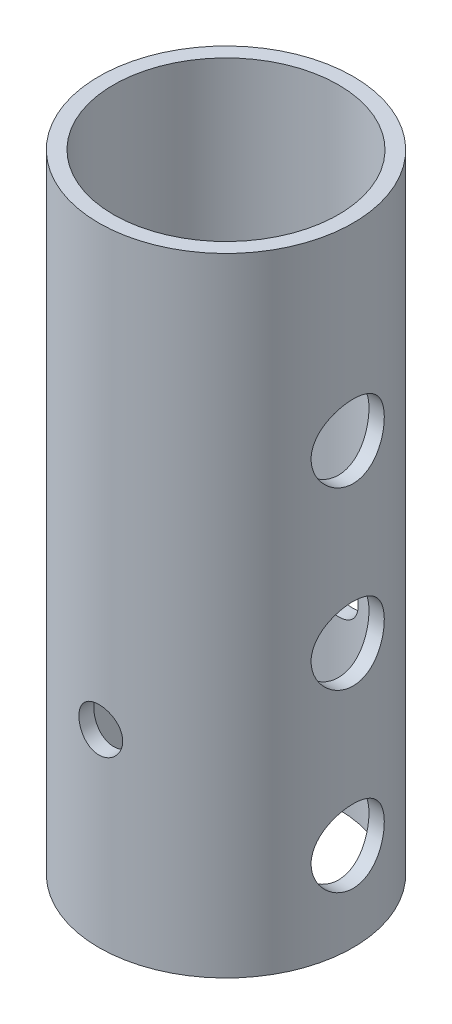
SolidWorks part; units mm, degrees
material "PTFE (general)"
ref_plane "Front Plane" through (0, 0, 0) normal (0, 0, 1) x (1, 0, 0)
ref_plane "Top Plane" through (0, 0, 0) normal (0, 1, 0) x (1, 0, 0)
ref_plane "Right Plane" through (0, 0, 0) normal (1, 0, 0) x (0, 0, -1)
sketch "Sketch1" plane through (0, 0, 0) normal (0, 1, 0) x (1, 0, 0)
  circle A0 centre (0, 0) radius 43.5
  circle A1 centre (0, 0) radius 38.5
  dimension "D1" = 87
  dimension "D2" = 77
extrude "Boss-Extrude1" add sketch "Sketch1" along normal blind 214.8
sketch "Sketch2" plane through (0, 0, 0) normal (1, 0, 0) x (0, 0, -1)
  line L0 (38.5, 214.8) -> (-38.5, 214.8) construction
  circle A0 centre (0, 150.1) radius 12.53
  circle A1 centre (0, 90.1) radius 12.53
  circle A2 centre (0, 30.1) radius 12.53
  dimension "D2" = 25.06
  dimension "D3" = 25.06
  dimension "D4" = 25.06
  dimension "D1" = 64.7
  dimension "D5" = 60
  dimension "D6" = 60
extrude "Cut-Extrude1" cut sketch "Sketch2" along normal through all
sketch "Sketch4" plane through (0, 0, 0) normal (0, 0, 1) x (1, 0, 0)
  line L0 (-43.5, 0) -> (43.5, 0) construction
  circle A0 centre (0, 64.6) radius 7.5
  dimension "D1" = 15
  dimension "D2" = 64.6
extrude "Cut-Extrude2" cut sketch "Sketch4" against normal through all both and the other way through all
